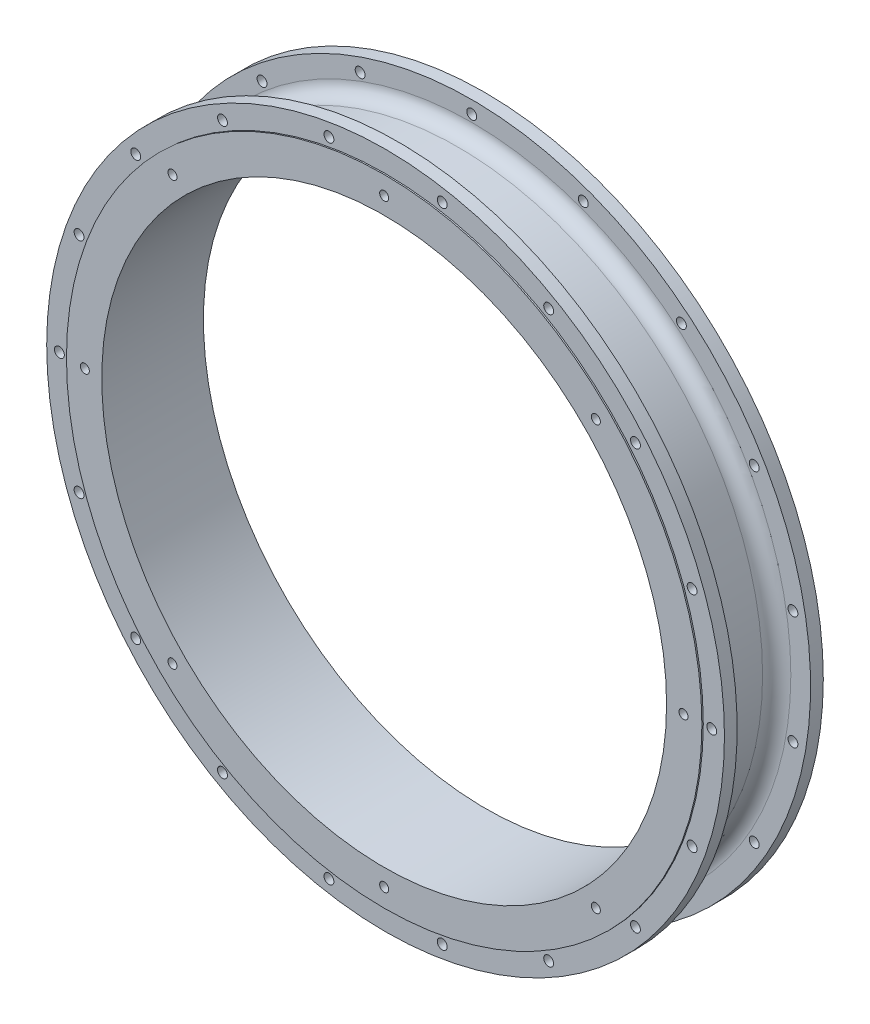
SolidWorks part; units mm, degrees
material "3.1305 (EN-AW 2117)"
ref_plane "Спереди" through (0, 0, 0) normal (0, 0, 1) x (1, 0, 0)
ref_plane "Сверху" through (0, 0, 0) normal (0, 1, 0) x (1, 0, 0)
ref_plane "Справа" through (0, 0, 0) normal (1, 0, 0) x (0, 0, -1)
sketch "Эскиз1" plane through (0, 0, 0) normal (0, 0, 1) x (1, 0, 0)
  circle A0 centre (0, 0) radius 120
extrude "Бобышка-Вытянуть1" add sketch "Эскиз1" along normal blind 35
sketch "Эскиз2" plane through (0, 0, 0) normal (0, 0, -1) x (-1, 0, 0)
  line L0 (0, 0) -> (-251.1474, 145) construction
  line L1 (0, 0) -> (-186.4084, 222.1529) construction
  line L2 (-186.4084, 222.1529) -> (-251.1474, 145) construction
  line L3 (0, 0) -> (-222.1529, 186.4084) construction
  circle A0 centre (0, 0) radius 115.5 construction
  circle A1 centre (0, 115.5) radius 1.75
  circle A2 centre (39.5033, 108.5345) radius 1.75
  circle A3 centre (74.242, 88.4781) radius 1.75
  circle A4 centre (100.0259, 57.75) radius 1.75
  circle A5 centre (113.7453, 20.0564) radius 1.75
  circle A6 centre (113.7453, -20.0564) radius 1.75
  circle A7 centre (100.0259, -57.75) radius 1.75
  circle A8 centre (74.242, -88.4781) radius 1.75
  circle A9 centre (39.5033, -108.5345) radius 1.75
  circle A10 centre (0, -115.5) radius 1.75
  circle A11 centre (-39.5033, -108.5345) radius 1.75
  circle A12 centre (-74.242, -88.4781) radius 1.75
  circle A13 centre (-100.0259, -57.75) radius 1.75
  circle A14 centre (-113.7453, -20.0564) radius 1.75
  circle A15 centre (-113.7453, 20.0564) radius 1.75
  circle A16 centre (-100.0259, 57.75) radius 1.75
  circle A17 centre (-74.242, 88.4781) radius 1.75
  circle A18 centre (-39.5033, 108.5345) radius 1.75
  point P42 (0, 0)
  dimension "D1" = 18
  dimension "D2" = 231
  dimension "D3" = 290
sketch "Эскиз4" plane through (0, 0, 35) normal (0, 0, 1) x (1, 0, 0)
  circle A0 centre (0, 0) radius 115.5 construction
  circle A1 centre (-115.5, 0) radius 1.75
  circle A2 centre (-108.5345, 39.5033) radius 1.75
  circle A3 centre (-88.4781, 74.242) radius 1.75
  circle A4 centre (-57.75, 100.0259) radius 1.75
  circle A5 centre (-20.0564, 113.7453) radius 1.75
  circle A6 centre (20.0564, 113.7453) radius 1.75
  circle A7 centre (57.75, 100.0259) radius 1.75
  circle A8 centre (88.4781, 74.242) radius 1.75
  circle A9 centre (108.5345, 39.5033) radius 1.75
  circle A10 centre (115.5, 0) radius 1.75
  circle A11 centre (108.5345, -39.5033) radius 1.75
  circle A12 centre (88.4781, -74.242) radius 1.75
  circle A13 centre (57.75, -100.0259) radius 1.75
  circle A14 centre (20.0564, -113.7453) radius 1.75
  circle A15 centre (-20.0564, -113.7453) radius 1.75
  circle A16 centre (-57.75, -100.0259) radius 1.75
  circle A17 centre (-88.4781, -74.242) radius 1.75
  circle A18 centre (-108.5345, -39.5033) radius 1.75
  point P42 (0, 0)
  dimension "D1" = 18
  dimension "D2" = 231
sketch "Эскиз5" plane through (0, 0, 35) normal (0, 0, 1) x (1, 0, 0)
  circle A0 centre (0, 0) radius 100
  dimension "D1" = 200
sketch "Эскиз6" plane through (0, 0, 0) normal (0, 0, -1) x (-1, 0, 0)
  circle A0 centre (0, 0) radius 112.5
sketch "Эскиз7" plane through (0, 0, 0) normal (0, 1, 0) x (1, 0, 0)
  line L0 (-120, 0) -> (-120, -4.5)
  line L1 (-120, 0) -> (-120, -35) construction
  line L2 (-120, -4.5) -> (-113, -4.5)
  line L3 (-108, -9.5) -> (-108, -25.5)
  line L4 (-113, -30.5) -> (-120, -30.5)
  line L5 (-120, -30.5) -> (-120, -35)
  line L6 (-120, -35) -> (-128.2207, -35)
  line L7 (-128.2207, -35) -> (-128.2207, 0)
  line L8 (-128.2207, 0) -> (-120, 0)
  arc A0 (-108, -25.5) -> (-113, -30.5) centre (-113, -25.5) cw
  arc A1 (-113, -4.5) -> (-108, -9.5) centre (-113, -9.5) cw
  dimension "D1" = 5
  dimension "D2" = 12
sketch "Эскиз8" plane through (0, 0, 0) normal (0, 1, 0) x (1, 0, 0)
  line L0 (0, 0) -> (0, -35)
revolve "Вырез-Повернуть2" cut sketch "Эскиз7" angle 360 about L0
sketch "Эскиз9" plane through (0, 0, 35) normal (0, 0, 1) x (1, 0, 0)
  circle A0 centre (0, 0) radius 112.5
extrude "Бобышка-Вытянуть2" add sketch "Эскиз9" along normal blind 0.5
extrude "Бобышка-Вытянуть3" add sketch "Эскиз6" along normal blind 0.5 contours A0
extrude "Вырез-Вытянуть2" cut sketch "Эскиз5" against normal through all both and the other way through all contours A0
extrude "Вырез-Вытянуть3" cut sketch "Эскиз4" against normal blind 5
extrude "Вырез-Вытянуть4" cut sketch "Эскиз2" against normal blind 5
sketch "Эскиз10" plane through (0, 0, -0.5) normal (0, 0, -1) x (-1, 0, 0)
  circle A0 centre (0, 0) radius 106 construction
  circle A1 centre (0, 106) radius 1.6
  circle A2 centre (74.9533, 74.9533) radius 1.6
  circle A3 centre (106, 0) radius 1.6
  circle A4 centre (74.9533, -74.9533) radius 1.6
  circle A5 centre (0, -106) radius 1.6
  circle A6 centre (-74.9533, -74.9533) radius 1.6
  circle A7 centre (-106, 0) radius 1.6
  circle A8 centre (-74.9533, 74.9533) radius 1.6
  point P21 (0, 0)
  dimension "D1" = 212
  dimension "D2" = 8
  dimension "D3" = 3.2
extrude "Вырез-Вытянуть6" cut sketch "Эскиз10" against normal blind 6
sketch "Эскиз11" plane through (0, 0, 0) normal (0, 0, 1) x (1, 0, 0)
  circle A0 centre (0, 0) radius 106 construction
  circle A1 centre (0, 106) radius 1.6
  circle A2 centre (74.9533, 74.9533) radius 1.6
  circle A3 centre (106, 0) radius 1.6
  circle A4 centre (74.9533, -74.9533) radius 1.6
  circle A5 centre (0, -106) radius 1.6
  circle A6 centre (-74.9533, -74.9533) radius 1.6
  circle A7 centre (-106, 0) radius 1.6
  circle A8 centre (-74.9533, 74.9533) radius 1.6
  point P21 (0, 0)
  dimension "D1" = 212
  dimension "D2" = 8
  dimension "D3" = 3.2
extrude "Вырез-Вытянуть7" cut sketch "Эскиз11" against normal blind 6.5 from offset 36
sketch3d "Трехмерный эскиз1"
  line L0 (-20.0564, 113.7453, 35) -> (-20.0564, 113.7453, 30.5)
  line L1 (-20.0564, 113.7453, 30.5) -> (-20.0564, 113.7453, 35) construction
  line L2 (-57.75, 100.0259, 35) -> (-57.75, 100.0259, 30.5)
  line L3 (-57.75, 100.0259, 30.5) -> (-57.75, 100.0259, 35) construction
  line L4 (20.0564, 113.7453, 35) -> (20.0564, 113.7453, 30.5)
  line L5 (20.0564, 113.7453, 30.5) -> (20.0564, 113.7453, 35) construction
  line L6 (57.75, 100.0259, 35) -> (57.75, 100.0259, 30.5)
  line L7 (57.75, 100.0259, 30.5) -> (57.75, 100.0259, 35) construction
  line L8 (88.4781, 74.242, 35) -> (88.4781, 74.242, 30.5)
  line L9 (88.4781, 74.242, 30.5) -> (88.4781, 74.242, 35) construction
  line L10 (108.5345, 39.5033, 35) -> (108.5345, 39.5033, 30.5)
  line L11 (108.5345, 39.5033, 30.5) -> (108.5345, 39.5033, 35) construction
  line L12 (115.5, 0, 35) -> (115.5, 0, 30.5)
  line L13 (115.5, 0, 30.5) -> (115.5, 0, 35) construction
  line L14 (108.5345, -39.5033, 35) -> (108.5345, -39.5033, 30.5)
  line L15 (108.5345, -39.5033, 30.5) -> (108.5345, -39.5033, 35) construction
  line L16 (88.4781, -74.242, 35) -> (88.4781, -74.242, 30.5)
  line L17 (88.4781, -74.242, 30.5) -> (88.4781, -74.242, 35) construction
  line L18 (57.75, -100.0259, 35) -> (57.75, -100.0259, 30.5)
  line L19 (57.75, -100.0259, 30.5) -> (57.75, -100.0259, 35) construction
  line L20 (20.0564, -113.7453, 35) -> (20.0564, -113.7453, 30.5)
  line L21 (20.0564, -113.7453, 30.5) -> (20.0564, -113.7453, 35) construction
  line L22 (-57.75, -100.0259, 35) -> (-57.75, -100.0259, 30.5)
  line L23 (-57.75, -100.0259, 30.5) -> (-57.75, -100.0259, 35) construction
  line L24 (-20.0564, -113.7453, 35) -> (-20.0564, -113.7453, 30.5)
  line L25 (-20.0564, -113.7453, 30.5) -> (-20.0564, -113.7453, 35) construction
  line L26 (-88.4781, -74.242, 35) -> (-88.4781, -74.242, 30.5)
  line L27 (-88.4781, -74.242, 30.5) -> (-88.4781, -74.242, 35) construction
  line L28 (-108.5345, -39.5033, 35) -> (-108.5345, -39.5033, 30.5)
  line L29 (-108.5345, -39.5033, 30.5) -> (-108.5345, -39.5033, 35) construction
  line L30 (-115.5, 0, 35) -> (-115.5, 0, 30.5)
  line L31 (-115.5, 0, 30.5) -> (-115.5, 0, 35) construction
  line L32 (-108.5345, 39.5033, 35) -> (-108.5345, 39.5033, 30.5)
  line L33 (-108.5345, 39.5033, 30.5) -> (-108.5345, 39.5033, 35) construction
  line L34 (-88.4781, 74.242, 35) -> (-88.4781, 74.242, 30.5)
  line L35 (-88.4781, 74.242, 30.5) -> (-88.4781, 74.242, 35) construction
  circle A0 centre (0, 0, 35) radius 115.5 construction
  point P29 (0, 0, 150.5)
sketch "Эскиз12" plane through (0, 0, 4.5) normal (0, 0, 1) x (1, 0, 0)
  circle A0 centre (0, 0) radius 115.5 construction
  circle A1 centre (0, 115.5) radius 1.75
  circle A2 centre (39.5033, 108.5345) radius 1.75
  circle A3 centre (74.242, 88.4781) radius 1.75
  circle A4 centre (100.0259, 57.75) radius 1.75
  circle A5 centre (113.7453, 20.0564) radius 1.75
  circle A6 centre (113.7453, -20.0564) radius 1.75
  circle A7 centre (100.0259, -57.75) radius 1.75
  circle A8 centre (74.242, -88.4781) radius 1.75
  circle A9 centre (39.5033, -108.5345) radius 1.75
  circle A10 centre (0, -115.5) radius 1.75
  circle A11 centre (-39.5033, -108.5345) radius 1.75
  circle A12 centre (-74.242, -88.4781) radius 1.75
  circle A13 centre (-100.0259, -57.75) radius 1.75
  circle A14 centre (-113.7453, -20.0564) radius 1.75
  circle A15 centre (-113.7453, 20.0564) radius 1.75
  circle A16 centre (-100.0259, 57.75) radius 1.75
  circle A17 centre (-74.242, 88.4781) radius 1.75
  circle A18 centre (-39.5033, 108.5345) radius 1.75
  point P42 (0, 0)
  dimension "D1" = 18
  dimension "D2" = 231
sketch "Эскиз14" plane through (0, 0, 30.5) normal (0, 0, 1) x (1, 0, 0)
  circle A0 centre (0, 0) radius 115.5 construction
  circle A1 centre (-115.5, 0) radius 1.75
  circle A2 centre (-108.5345, 39.5033) radius 1.75
  circle A3 centre (-88.4781, 74.242) radius 1.75
  circle A4 centre (-57.75, 100.0259) radius 1.75
  circle A5 centre (-20.0564, 113.7453) radius 1.75
  circle A6 centre (20.0564, 113.7453) radius 1.75
  circle A7 centre (57.75, 100.0259) radius 1.75
  circle A8 centre (88.4781, 74.242) radius 1.75
  circle A9 centre (108.5345, 39.5033) radius 1.75
  circle A10 centre (115.5, 0) radius 1.75
  circle A11 centre (108.5345, -39.5033) radius 1.75
  circle A12 centre (88.4781, -74.242) radius 1.75
  circle A13 centre (57.75, -100.0259) radius 1.75
  circle A14 centre (20.0564, -113.7453) radius 1.75
  circle A15 centre (-20.0564, -113.7453) radius 1.75
  circle A16 centre (-57.75, -100.0259) radius 1.75
  circle A17 centre (-88.4781, -74.242) radius 1.75
  circle A18 centre (-108.5345, -39.5033) radius 1.75
  point P42 (0, 0)
  dimension "D1" = 18
  dimension "D2" = 231
